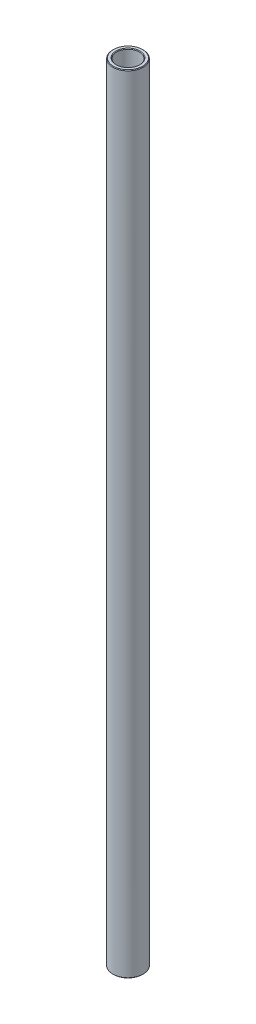
SolidWorks part; units mm, degrees
ref_plane "Front Plane" through (0, 0, 0) normal (0, 0, 1) x (1, 0, 0)
ref_plane "Top Plane" through (0, 0, 0) normal (0, 1, 0) x (1, 0, 0)
ref_plane "Right Plane" through (0, 0, 0) normal (1, 0, 0) x (0, 0, -1)
sketch "Sketch1" plane through (0, 0, 0) normal (0, 0, 1) x (1, 0, 0)
  line L0 (0, 11.6086) -> (0, -11.6086) construction
  line L1 (4.7625, 165.1) -> (6.35, 165.1)
  line L2 (6.35, 165.1) -> (6.35, -165.1)
  line L3 (6.35, -165.1) -> (4.7625, -165.1)
  line L4 (4.7625, -165.1) -> (4.7625, 165.1)
  line L5 (4.7625, 0) -> (0, 0) construction
  dimension "D1" = 9.525
  dimension "D2" = 12.7
  dimension "D3" = 330.2
revolve "Revolve1" add sketch "Sketch1" angle 360 about L0
chamfer "Chamfer1" distance 0.254 angle 45 4 edges at (-4.7625, -165.1, 0) (-6.35, -165.1, 0) (-6.35, 165.1, 0) (-4.7625, 165.1, 0)
